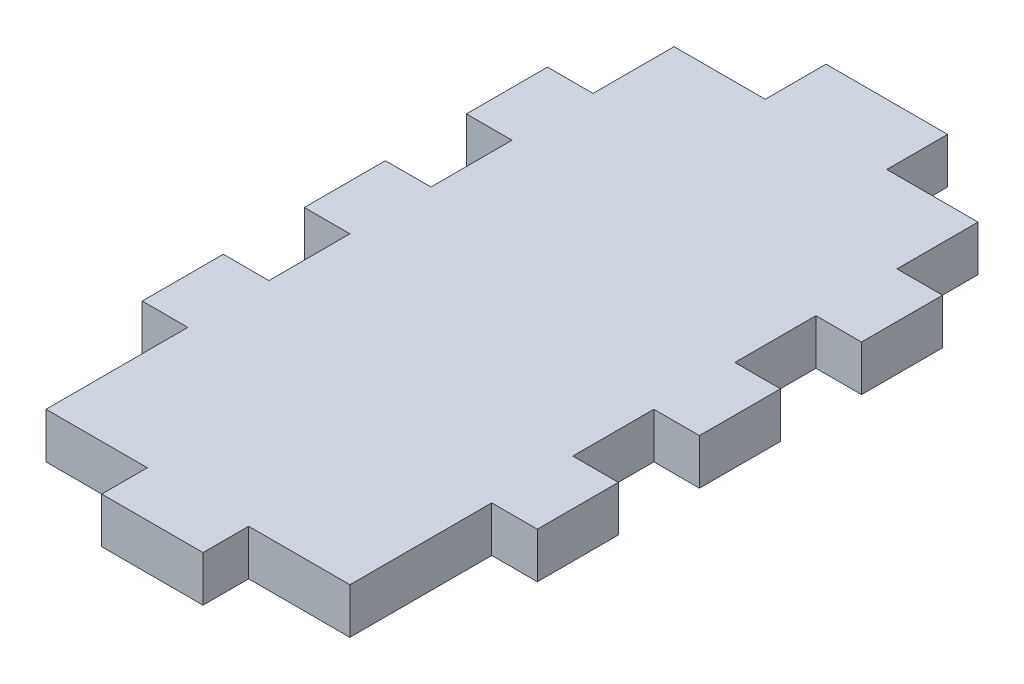
SolidWorks part; units mm, degrees
ref_plane "Front Plane" through (0, 0, 0) normal (0, 0, 1) x (1, 0, 0)
ref_plane "Top Plane" through (0, 0, 0) normal (0, 1, 0) x (1, 0, 0)
ref_plane "Right Plane" through (0, 0, 0) normal (1, 0, 0) x (0, 0, -1)
other "Configuration Table"
sketch "Sketch1" plane through (0, 0, 0) normal (0, 1, 0) x (1, 0, 0)
  line L0 (0, 30) -> (0, -30) construction
  line L7 (-15, 22) -> (-19.5, 22)
  line L9 (-15, 14) -> (-19.5, 14)
  line L10 (-19.5, 22) -> (-19.5, 14)
  line L11 (-15, 6) -> (-19.5, 6)
  line L13 (-15, -2) -> (-19.5, -2)
  line L14 (-19.5, 6) -> (-19.5, -2)
  line L15 (-15, -18) -> (-15, -32)
  line L16 (-15, -10) -> (-19.5, -10)
  line L18 (-15, -18) -> (-19.5, -18)
  line L19 (-19.5, -10) -> (-19.5, -18)
  line L36 (5, -32) -> (5, -36.5)
  line L41 (-15, -10) -> (-15, -2)
  line L42 (-15, 6) -> (-15, 14)
  line L43 (-15, 22) -> (-15, 30)
  line L47 (-15, 30) -> (-6, 30)
  line L49 (-6, 30) -> (-6, 36)
  line L50 (-6, 36) -> (6, 36)
  line L51 (6, 30) -> (6, 36)
  line L52 (6, 30) -> (15, 30)
  line L53 (15, -18) -> (15, -32)
  line L54 (15, -18) -> (19.5, -18)
  line L55 (19.5, -10) -> (19.5, -18)
  line L56 (15, -10) -> (19.5, -10)
  line L57 (15, -10) -> (15, -2)
  line L58 (15, -2) -> (19.5, -2)
  line L59 (19.5, 6) -> (19.5, -2)
  line L60 (15, 6) -> (19.5, 6)
  line L61 (15, 6) -> (15, 14)
  line L62 (15, 14) -> (19.5, 14)
  line L63 (19.5, 22) -> (19.5, 14)
  line L64 (15, 22) -> (19.5, 22)
  line L65 (15, 22) -> (15, 30)
  line L67 (-15, -32) -> (-5, -32)
  line L70 (-5, -36.5) -> (5, -36.5)
  line L71 (5, -32) -> (5, -36.5)
  line L72 (-5, -32) -> (-5, -36.5)
  line L73 (5, -32) -> (15, -32)
  point P0 (0, 0)
  point P3 (0, 0)
  point P22 (0, 0)
  dimension "D2" = 62
  dimension "D3" = 8
  dimension "D4" = 8
  dimension "D5" = 4.5
  dimension "D7" = 8
  dimension "D8" = 8
  dimension "D9" = 8
  dimension "D10" = 12
  dimension "D11" = 4.5
  dimension "D12" = 10
  dimension "D13" = 10
  dimension "D14" = 6
  dimension "D16" = 10
extrude "Boss-Extrude2" add sketch "Sketch1" along normal blind 4.5 contours L16 L19 L18 | L7 L10 L9 | L73 L53 L54 L55 L56 L57 L58 L59 L60 L61 L62 L63 L64 L65 L52 L51 L50 L49 L47 L43 L7 L10 L9 L42 L11 L14 L13 L41 L16 L19 L18 L15 L67 L72 L70 L36 region at (0, 0, 0.2705)
